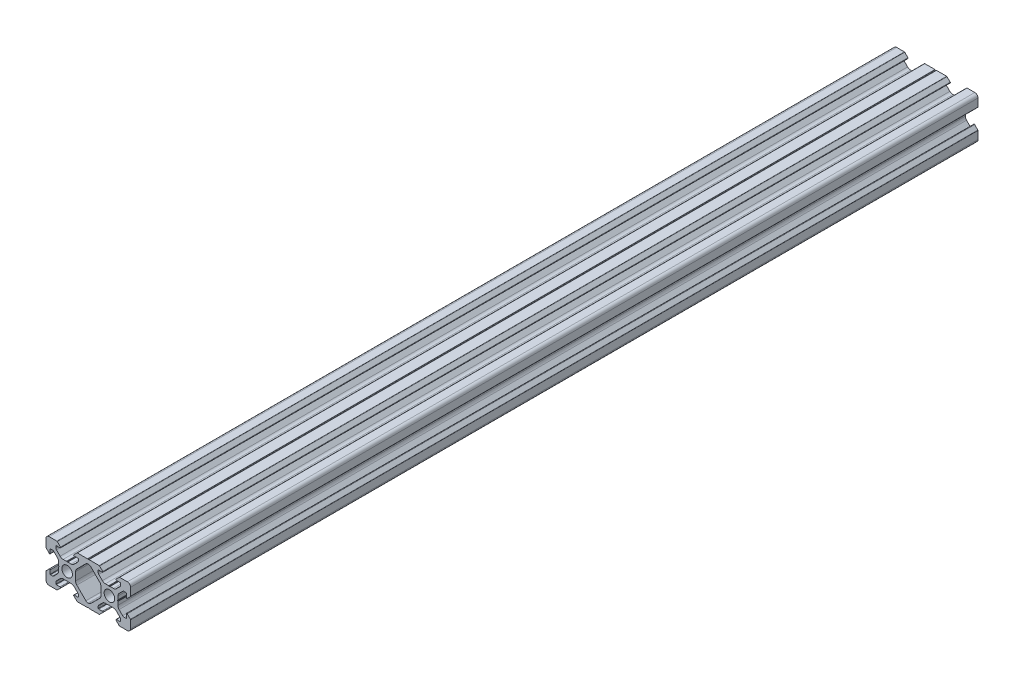
SolidWorks part; units mm, degrees
material "6063-T5"
ref_plane "Спереди" through (0, 0, 0) normal (0, 0, 1) x (1, 0, 0)
ref_plane "Сверху" through (0, 0, 0) normal (0, 1, 0) x (1, 0, 0)
ref_plane "Справа" through (0, 0, 0) normal (1, 0, 0) x (0, 0, -1)
sketch "Model" plane through (0, 0, 0) normal (0, 0, 1) x (1, 0, 0)
  line L0 (-5.4142, 2.9753) -> (-1.1373, 7.2523)
  line L1 (-6, -2.2365) -> (-6, 1.5611)
  line L2 (-5.4142, -3.6507) -> (-1.1373, -7.9276)
  line L3 (-0.1473, -8.3377) -> (0.1473, -8.3377)
  line L4 (5.4142, -3.6507) -> (1.1373, -7.9276)
  line L5 (6, -2.2365) -> (6, 1.5611)
  line L6 (5.4142, 2.9753) -> (1.1373, 7.2523)
  line L7 (-0.1473, 7.6623) -> (0.1473, 7.6623)
  line L8 (0.3757, 9.6623) -> (5.17, 9.6623)
  line L9 (5.3468, 9.5891) -> (6.8468, 8.0891)
  line L10 (6.67, 7.6623) -> (4.9, 7.6623)
  line L11 (4.7, 7.4623) -> (4.7, 6.6493)
  line L12 (4.9929, 5.9422) -> (6.687, 4.2481)
  line L13 (8.1012, 3.6623) -> (9.6623, 3.6623)
  line L14 (9.8185, 3.6075) -> (10, 3.4623)
  line L15 (10.1815, 3.6075) -> (10, 3.4623)
  line L16 (13.313, 4.2481) -> (15.0071, 5.9422)
  line L17 (15.3, 6.6493) -> (15.3, 7.4623)
  line L18 (15.1, 7.6623) -> (13.33, 7.6623)
  line L19 (14.6532, 9.5891) -> (13.1532, 8.0891)
  line L20 (14.83, 9.6623) -> (18.5, 9.6623)
  line L21 (20, 4.4923) -> (20, 8.1623)
  line L22 (19.9268, 4.3155) -> (18.4268, 2.8155)
  line L23 (18, 4.7623) -> (18, 2.9923)
  line L24 (16.987, 4.9623) -> (17.8, 4.9623)
  line L25 (14.5858, 2.9753) -> (16.2799, 4.6694)
  line L26 (14, 0) -> (14, 1.5611)
  line L27 (13.9452, -0.1562) -> (13.8, -0.3377)
  line L28 (13.9452, -0.5192) -> (13.8, -0.3377)
  line L29 (14, -0.6754) -> (14, -2.2365)
  line L30 (14.5858, -3.6507) -> (16.2799, -5.3448)
  line L31 (16.987, -5.6377) -> (17.8, -5.6377)
  line L32 (18, -5.4377) -> (18, -3.6677)
  line L33 (19.9268, -4.9909) -> (18.4268, -3.4909)
  line L34 (20, -5.1677) -> (20, -8.8377)
  line L35 (14.83, -10.3377) -> (18.5, -10.3377)
  line L36 (14.6532, -10.2645) -> (13.1532, -8.7645)
  line L37 (15.1, -8.3377) -> (13.33, -8.3377)
  line L38 (15.3, -7.3247) -> (15.3, -8.1377)
  line L39 (13.313, -4.9235) -> (15.0071, -6.6176)
  line L40 (10.3377, -4.3377) -> (11.8988, -4.3377)
  line L41 (10.1815, -4.2829) -> (10, -4.1377)
  line L42 (9.8185, -4.2829) -> (10, -4.1377)
  line L43 (8.1012, -4.3377) -> (9.6623, -4.3377)
  line L44 (4.9929, -6.6176) -> (6.687, -4.9235)
  line L45 (4.7, -8.1377) -> (4.7, -7.3247)
  line L46 (6.67, -8.3377) -> (4.9, -8.3377)
  line L47 (5.3468, -10.2645) -> (6.8468, -8.7645)
  line L48 (0.3757, -10.3377) -> (5.17, -10.3377)
  line L49 (0, -10.1377) -> (0.237, -10.2957)
  line L50 (0, -10.1377) -> (-0.237, -10.2957)
  line L51 (-0.3757, -10.3377) -> (-5.17, -10.3377)
  line L52 (-5.3468, -10.2645) -> (-6.8468, -8.7645)
  line L53 (-6.67, -8.3377) -> (-4.9, -8.3377)
  line L54 (-4.7, -8.1377) -> (-4.7, -7.3247)
  line L55 (-4.9929, -6.6176) -> (-6.687, -4.9235)
  line L56 (-8.1012, -4.3377) -> (-9.6623, -4.3377)
  line L57 (-9.8185, -4.2829) -> (-10, -4.1377)
  line L58 (-10.1815, -4.2829) -> (-10, -4.1377)
  line L59 (-10.3377, -4.3377) -> (-11.8988, -4.3377)
  line L60 (-13.313, -4.9235) -> (-15.0071, -6.6176)
  line L61 (-15.3, -7.3247) -> (-15.3, -8.1377)
  line L62 (-15.1, -8.3377) -> (-13.33, -8.3377)
  line L63 (-14.6532, -10.2645) -> (-13.1532, -8.7645)
  line L64 (-14.83, -10.3377) -> (-18.5, -10.3377)
  line L65 (-20, -5.1677) -> (-20, -8.8377)
  line L66 (-19.9268, -4.9909) -> (-18.4268, -3.4909)
  line L67 (-18, -5.4377) -> (-18, -3.6677)
  line L68 (-16.987, -5.6377) -> (-17.8, -5.6377)
  line L69 (-14.5858, -3.6507) -> (-16.2799, -5.3448)
  line L70 (-14, -0.6754) -> (-14, -2.2365)
  line L71 (-13.9452, -0.5192) -> (-13.8, -0.3377)
  line L72 (-13.9452, -0.1562) -> (-13.8, -0.3377)
  line L73 (-14, 0) -> (-14, 1.5611)
  line L74 (-14.5858, 2.9753) -> (-16.2799, 4.6694)
  line L75 (-16.987, 4.9623) -> (-17.8, 4.9623)
  line L76 (-18, 4.7623) -> (-18, 2.9923)
  line L77 (-19.9268, 4.3155) -> (-18.4268, 2.8155)
  line L78 (-20, 4.4923) -> (-20, 8.1623)
  line L79 (-14.6532, 9.5891) -> (-13.1532, 8.0891)
  line L80 (-10.1815, 3.6075) -> (-10, 3.4623)
  line L81 (-9.8185, 3.6075) -> (-10, 3.4623)
  line L82 (-8.1012, 3.6623) -> (-9.6623, 3.6623)
  line L83 (-4.9929, 5.9422) -> (-6.687, 4.2481)
  line L84 (-4.7, 7.4623) -> (-4.7, 6.6493)
  line L85 (-6.67, 7.6623) -> (-4.9, 7.6623)
  line L86 (-5.3468, 9.5891) -> (-6.8468, 8.0891)
  line L87 (-0.3757, 9.6623) -> (-5.17, 9.6623)
  line L88 (0, 9.4623) -> (-0.237, 9.6203)
  line L89 (0, 9.4623) -> (0.237, 9.6203)
  line L90 (10.3377, 3.6623) -> (11.8988, 3.6623)
  line L91 (-10.3377, 3.6623) -> (-11.8988, 3.6623)
  line L92 (-13.313, 4.2481) -> (-15.0071, 5.9422)
  line L93 (-15.3, 6.6493) -> (-15.3, 7.4623)
  line L94 (-15.1, 7.6623) -> (-13.33, 7.6623)
  line L95 (-14.83, 9.6623) -> (-18.5, 9.6623)
  circle A0 centre (10, -0.3377) radius 2.5
  arc A1 (-0.1473, 7.6623) -> (-1.1373, 7.2523) centre (-0.1473, 6.2623) ccw
  arc A2 (-5.4142, 2.9753) -> (-6, 1.5611) centre (-4, 1.5611) ccw
  arc A3 (-6, -2.2365) -> (-5.4142, -3.6507) centre (-4, -2.2365) ccw
  arc A4 (-1.1373, -7.9276) -> (-0.1473, -8.3377) centre (-0.1473, -6.9377) ccw
  arc A5 (0.1473, -8.3377) -> (1.1373, -7.9276) centre (0.1473, -6.9377) ccw
  arc A6 (5.4142, -3.6507) -> (6, -2.2365) centre (4, -2.2365) ccw
  arc A7 (6, 1.5611) -> (5.4142, 2.9753) centre (4, 1.5611) ccw
  arc A8 (1.1373, 7.2523) -> (0.1473, 7.6623) centre (0.1473, 6.2623) ccw
  arc A9 (0.3757, 9.6623) -> (0.237, 9.6203) centre (0.3757, 9.4123) ccw
  arc A10 (5.3468, 9.5891) -> (5.17, 9.6623) centre (5.17, 9.4123) ccw
  arc A11 (6.67, 7.6623) -> (6.8468, 8.0891) centre (6.67, 7.9123) ccw
  arc A12 (4.9, 7.6623) -> (4.7, 7.4623) centre (4.9, 7.4623) ccw
  arc A13 (4.7, 6.6493) -> (4.9929, 5.9422) centre (5.7, 6.6493) ccw
  arc A14 (6.687, 4.2481) -> (8.1012, 3.6623) centre (8.1012, 5.6623) ccw
  arc A15 (9.8185, 3.6075) -> (9.6623, 3.6623) centre (9.6623, 3.4123) ccw
  arc A16 (10.3377, 3.6623) -> (10.1815, 3.6075) centre (10.3377, 3.4123) ccw
  arc A17 (11.8988, 3.6623) -> (13.313, 4.2481) centre (11.8988, 5.6623) ccw
  arc A18 (15.0071, 5.9422) -> (15.3, 6.6493) centre (14.3, 6.6493) ccw
  arc A19 (15.3, 7.4623) -> (15.1, 7.6623) centre (15.1, 7.4623) ccw
  arc A20 (13.1532, 8.0891) -> (13.33, 7.6623) centre (13.33, 7.9123) ccw
  arc A21 (14.83, 9.6623) -> (14.6532, 9.5891) centre (14.83, 9.4123) ccw
  arc A22 (20, 8.1623) -> (18.5, 9.6623) centre (18.5, 8.1623) ccw
  arc A23 (19.9268, 4.3155) -> (20, 4.4923) centre (19.75, 4.4923) ccw
  arc A24 (18, 2.9923) -> (18.4268, 2.8155) centre (18.25, 2.9923) ccw
  arc A25 (18, 4.7623) -> (17.8, 4.9623) centre (17.8, 4.7623) ccw
  arc A26 (16.987, 4.9623) -> (16.2799, 4.6694) centre (16.987, 3.9623) ccw
  arc A27 (14.5858, 2.9753) -> (14, 1.5611) centre (16, 1.5611) ccw
  arc A28 (13.9452, -0.1562) -> (14, 0) centre (13.75, 0) ccw
  arc A29 (14, -0.6754) -> (13.9452, -0.5192) centre (13.75, -0.6754) ccw
  arc A30 (14, -2.2365) -> (14.5858, -3.6507) centre (16, -2.2365) ccw
  arc A31 (16.2799, -5.3448) -> (16.987, -5.6377) centre (16.987, -4.6377) ccw
  arc A32 (17.8, -5.6377) -> (18, -5.4377) centre (17.8, -5.4377) ccw
  arc A33 (18.4268, -3.4909) -> (18, -3.6677) centre (18.25, -3.6677) ccw
  arc A34 (20, -5.1677) -> (19.9268, -4.9909) centre (19.75, -5.1677) ccw
  arc A35 (18.5, -10.3377) -> (20, -8.8377) centre (18.5, -8.8377) ccw
  arc A36 (14.6532, -10.2645) -> (14.83, -10.3377) centre (14.83, -10.0877) ccw
  arc A37 (13.33, -8.3377) -> (13.1532, -8.7645) centre (13.33, -8.5877) ccw
  arc A38 (15.1, -8.3377) -> (15.3, -8.1377) centre (15.1, -8.1377) ccw
  arc A39 (15.3, -7.3247) -> (15.0071, -6.6176) centre (14.3, -7.3247) ccw
  arc A40 (13.313, -4.9235) -> (11.8988, -4.3377) centre (11.8988, -6.3377) ccw
  arc A41 (10.1815, -4.2829) -> (10.3377, -4.3377) centre (10.3377, -4.0877) ccw
  arc A42 (9.6623, -4.3377) -> (9.8185, -4.2829) centre (9.6623, -4.0877) ccw
  arc A43 (8.1012, -4.3377) -> (6.687, -4.9235) centre (8.1012, -6.3377) ccw
  arc A44 (4.9929, -6.6176) -> (4.7, -7.3247) centre (5.7, -7.3247) ccw
  arc A45 (4.7, -8.1377) -> (4.9, -8.3377) centre (4.9, -8.1377) ccw
  arc A46 (6.8468, -8.7645) -> (6.67, -8.3377) centre (6.67, -8.5877) ccw
  arc A47 (5.17, -10.3377) -> (5.3468, -10.2645) centre (5.17, -10.0877) ccw
  arc A48 (0.237, -10.2957) -> (0.3757, -10.3377) centre (0.3757, -10.0877) ccw
  arc A49 (-0.3757, -10.3377) -> (-0.237, -10.2957) centre (-0.3757, -10.0877) ccw
  arc A50 (-5.3468, -10.2645) -> (-5.17, -10.3377) centre (-5.17, -10.0877) ccw
  arc A51 (-6.67, -8.3377) -> (-6.8468, -8.7645) centre (-6.67, -8.5877) ccw
  arc A52 (-4.9, -8.3377) -> (-4.7, -8.1377) centre (-4.9, -8.1377) ccw
  arc A53 (-4.7, -7.3247) -> (-4.9929, -6.6176) centre (-5.7, -7.3247) ccw
  arc A54 (-6.687, -4.9235) -> (-8.1012, -4.3377) centre (-8.1012, -6.3377) ccw
  arc A55 (-9.8185, -4.2829) -> (-9.6623, -4.3377) centre (-9.6623, -4.0877) ccw
  arc A56 (-10.3377, -4.3377) -> (-10.1815, -4.2829) centre (-10.3377, -4.0877) ccw
  arc A57 (-11.8988, -4.3377) -> (-13.313, -4.9235) centre (-11.8988, -6.3377) ccw
  arc A58 (-15.0071, -6.6176) -> (-15.3, -7.3247) centre (-14.3, -7.3247) ccw
  arc A59 (-15.3, -8.1377) -> (-15.1, -8.3377) centre (-15.1, -8.1377) ccw
  arc A60 (-13.1532, -8.7645) -> (-13.33, -8.3377) centre (-13.33, -8.5877) ccw
  arc A61 (-14.83, -10.3377) -> (-14.6532, -10.2645) centre (-14.83, -10.0877) ccw
  arc A62 (-20, -8.8377) -> (-18.5, -10.3377) centre (-18.5, -8.8377) ccw
  arc A63 (-19.9268, -4.9909) -> (-20, -5.1677) centre (-19.75, -5.1677) ccw
  arc A64 (-18, -3.6677) -> (-18.4268, -3.4909) centre (-18.25, -3.6677) ccw
  arc A65 (-18, -5.4377) -> (-17.8, -5.6377) centre (-17.8, -5.4377) ccw
  arc A66 (-16.987, -5.6377) -> (-16.2799, -5.3448) centre (-16.987, -4.6377) ccw
  arc A67 (-14.5858, -3.6507) -> (-14, -2.2365) centre (-16, -2.2365) ccw
  arc A68 (-13.9452, -0.5192) -> (-14, -0.6754) centre (-13.75, -0.6754) ccw
  arc A69 (-14, 0) -> (-13.9452, -0.1562) centre (-13.75, 0) ccw
  arc A70 (-14, 1.5611) -> (-14.5858, 2.9753) centre (-16, 1.5611) ccw
  arc A71 (-16.2799, 4.6694) -> (-16.987, 4.9623) centre (-16.987, 3.9623) ccw
  arc A72 (-17.8, 4.9623) -> (-18, 4.7623) centre (-17.8, 4.7623) ccw
  arc A73 (-18.4268, 2.8155) -> (-18, 2.9923) centre (-18.25, 2.9923) ccw
  arc A74 (-20, 4.4923) -> (-19.9268, 4.3155) centre (-19.75, 4.4923) ccw
  arc A75 (-18.5, 9.6623) -> (-20, 8.1623) centre (-18.5, 8.1623) ccw
  arc A76 (-14.6532, 9.5891) -> (-14.83, 9.6623) centre (-14.83, 9.4123) ccw
  arc A77 (-13.33, 7.6623) -> (-13.1532, 8.0891) centre (-13.33, 7.9123) ccw
  arc A78 (-15.1, 7.6623) -> (-15.3, 7.4623) centre (-15.1, 7.4623) ccw
  arc A79 (-15.3, 6.6493) -> (-15.0071, 5.9422) centre (-14.3, 6.6493) ccw
  arc A80 (-13.313, 4.2481) -> (-11.8988, 3.6623) centre (-11.8988, 5.6623) ccw
  arc A81 (-10.1815, 3.6075) -> (-10.3377, 3.6623) centre (-10.3377, 3.4123) ccw
  arc A82 (-9.6623, 3.6623) -> (-9.8185, 3.6075) centre (-9.6623, 3.4123) ccw
  arc A83 (-8.1012, 3.6623) -> (-6.687, 4.2481) centre (-8.1012, 5.6623) ccw
  arc A84 (-4.9929, 5.9422) -> (-4.7, 6.6493) centre (-5.7, 6.6493) ccw
  arc A85 (-4.7, 7.4623) -> (-4.9, 7.6623) centre (-4.9, 7.4623) ccw
  arc A86 (-6.8468, 8.0891) -> (-6.67, 7.6623) centre (-6.67, 7.9123) ccw
  arc A87 (-5.17, 9.6623) -> (-5.3468, 9.5891) centre (-5.17, 9.4123) ccw
  arc A88 (-0.237, 9.6203) -> (-0.3757, 9.6623) centre (-0.3757, 9.4123) ccw
  circle A89 centre (-10, -0.3377) radius 2.5
  dimension "D1" = 20
  dimension "D2" = 40
  dimension "D3" = 20
extrude "Body" add sketch "Model" along normal blind 401
hole_wizard "Tap Drill for M6x1.0 Tap1" positions "Sketch4" profile "Sketch5" hole size "M6x1.0" standard "ANSI Metric"
sketch "Sketch4" plane through (0, 0, 401) normal (0, 0, 1) x (1, 0, 0)
  point P0 (-10, -0.3377)
  point P3 (10, -0.3377)
  point P8 (-10, -0.3377)
  point P10 (10, -0.3377)
  point P16 (10, -0.3377)
  point P18 (-10, -0.3377)
sketch "Sketch5" plane through (-10, -0.3377, 401) normal (1, 0, 0) x (0, -1, 0)
  line L0 (0, 0) -> (0, 15)
  line L1 (0, 15) -> (2.5, 13.4978)
  line L2 (2.5, 13.4978) -> (2.5, 0)
  line L5 (2.5, 0) -> (0, 0)
  line L10 (0, 15) -> (-2.5, 13.4978) construction
  line L11 (0, -6.35) -> (0, 107.95) construction
  dimension "Hole Dia." = 5
  dimension "Hole Depth" = 15
  dimension "Drill Angle" = 118
hole_wizard "Tap Drill for M6x1.0 Tap2" positions "Sketch6" profile "Sketch7" hole size "M6x1.0" standard "ANSI Metric"
sketch "Sketch6" plane through (0, 0, 0) normal (0, 0, -1) x (-1, 0, 0)
  point P0 (-10, -0.3377)
  point P3 (10, -0.3377)
sketch "Sketch7" plane through (10, -0.3377, 0) normal (1, 0, 0) x (0, 1, 0)
  line L0 (0, 0) -> (0, 15)
  line L1 (0, 15) -> (2.5, 13.4978)
  line L2 (2.5, 13.4978) -> (2.5, 0)
  line L5 (2.5, 0) -> (0, 0)
  line L10 (0, 15) -> (-2.5, 13.4978) construction
  line L11 (0, -6.35) -> (0, 107.95) construction
  dimension "Hole Dia." = 5
  dimension "Hole Depth" = 15
  dimension "Drill Angle" = 118
